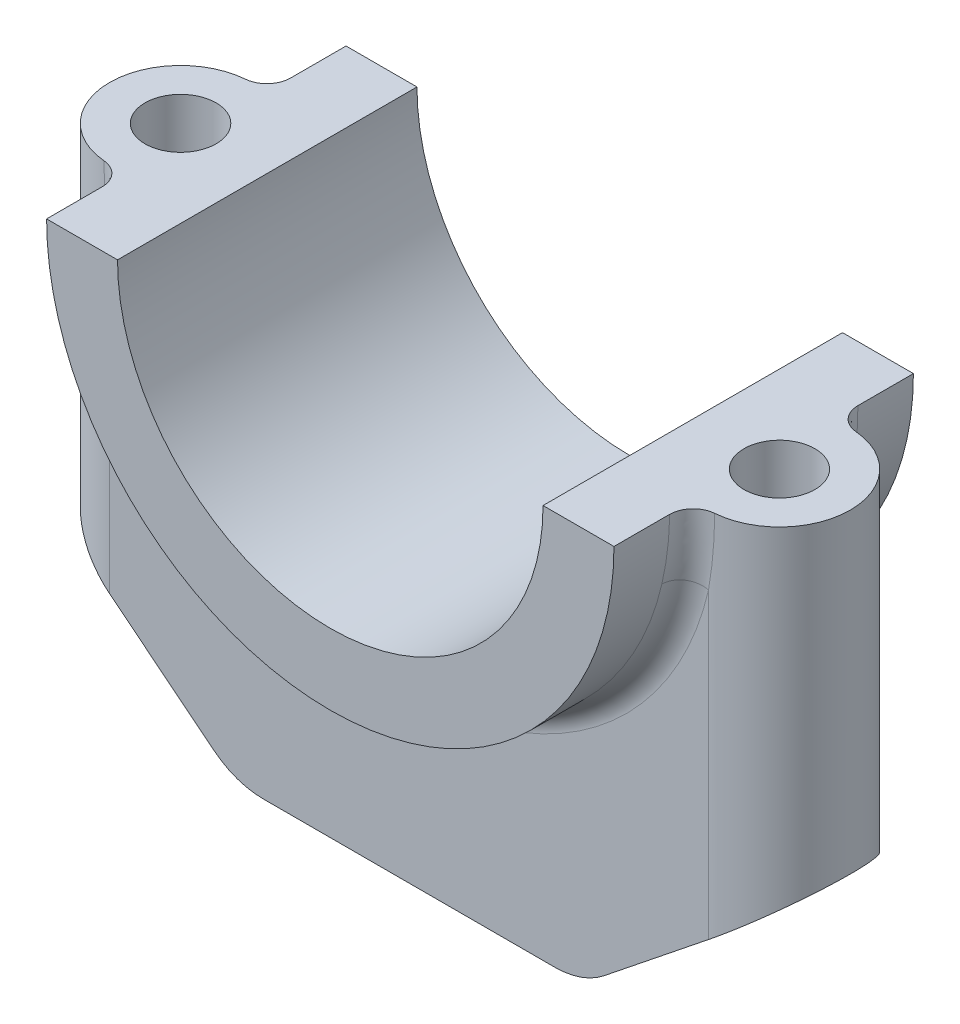
SolidWorks part; units mm, degrees
ref_plane "Front Plane" through (0, 0, 0) normal (0, 0, 1) x (1, 0, 0)
ref_plane "Top Plane" through (0, 0, 0) normal (0, 1, 0) x (1, 0, 0)
ref_plane "Right Plane" through (0, 0, 0) normal (1, 0, 0) x (0, 0, -1)
sketch "Sketch1" plane through (0, 0, 0) normal (0, 0, 1) x (1, 0, 0)
  line L0 (-36, 0) -> (-27, 0)
  line L1 (-36, 0) -> (-36, -60)
  line L2 (-36, -60) -> (36, -60)
  line L3 (36, -60) -> (36, 0)
  line L4 (27, 0) -> (36, 0)
  arc A0 (-27, 0) -> (27, 0) centre (0, 0) ccw
  arc A1 (-36, 0) -> (36, 0) centre (0, 0) ccw
  dimension "D1" = 54
  dimension "D2" = 72
  dimension "D3" = 60
extrude "Boss-Extrude1" add sketch "Sketch1" along normal mid plane 38 contours L0 A1 L4 A0 region at (-31.5, -0.805, 0)
extrude "Boss-Extrude2" add sketch "Sketch1<3>" along normal mid plane 18 contours A1 L1 L2 L3 region at (0, -43.1197, 0)
sketch "Sketch1<3>" plane through (0, 0, 0) normal (0, 0, 1) x (1, 0, 0) same geometry as "Sketch1"
sketch "Sketch2" plane through (0, -60, 0) normal (0, -1, 0) x (1, 0, 0)
  line L0 (0, 24.1351) -> (0, -24.37) construction
  line L1 (-38, 9) -> (38, 9)
  line L2 (-41.8694, 0) -> (49.5033, 0) construction
  line L3 (-38, -9) -> (38, -9)
  arc A0 (-38, 9) -> (-38, -9) centre (-38, 0) ccw
  circle A1 centre (-38, 0) radius 4.5
  arc A2 (38, -9) -> (38, 9) centre (38, 0) ccw
  circle A3 centre (38, 0) radius 4.5
  dimension "D1" = 18
  dimension "D2" = 9
  dimension "D3" = 76
  dimension "D4" = 38
extrude "Boss-Extrude3" add sketch "Sketch2" against normal up to surface (60 mm away) up to face at (-33, 0, 0)
sketch "Sketch3" plane through (0, 0, -9) normal (0, 0, -1) x (-1, 0, 0)
  line L1 (27, 0) -> (-27, 0)
  line L2 (27, 0) -> (-27, 0)
  arc A1 (-27, 0) -> (27, 0) centre (0, 0) ccw
  arc A2 (-27, 0) -> (27, 0) centre (0, 0) ccw
  dimension "D1" = 0
extrude "Cut-Extrude1" cut sketch "Sketch3" against normal blind 18
sketch "Sketch4" plane through (0, 0, 0) normal (0, 1, 0) x (1, 0, 0)
  circle A0 centre (-38, 0) radius 4.5115
  circle A1 centre (38, 0) radius 4.5
extrude "Cut-Extrude2" cut sketch "Sketch4" against normal blind 68
sketch "Sketch5" plane through (0, 0, 0) normal (0, 0, 1) x (1, 0, 0)
  line L1 (-47, -60) -> (-22, -60)
  line L3 (-38, -60) -> (38, -60) construction
  line L5 (-22, -60) -> (-47, -40)
  line L6 (-47, -60) -> (-47, -40)
  line L7 (0, 0) -> (0, -95.6251) construction
  line L8 (47, -60) -> (47, -40)
  line L9 (22, -60) -> (47, -40)
  line L10 (47, -60) -> (22, -60)
  dimension "D1" = 20
  dimension "D2" = 25
extrude "Cut-Extrude3" cut sketch "Sketch5" against normal mid plane 68
fillet "Fillet1" radius 10 2 edges at (22, -60, 0) (-22, -60, 0)
fillet "Fillet2" radius 3 2 edges at (0, -36, 9) (0, -36, -9)
